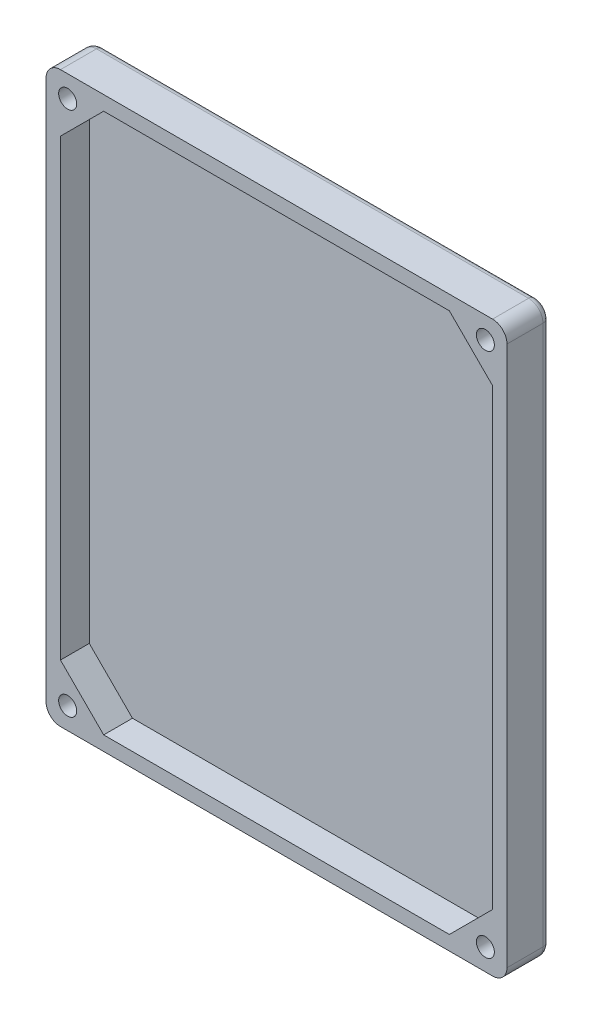
SolidWorks part; units mm, degrees
ref_plane "Front Plane" through (0, 0, 0) normal (0, 0, 1) x (1, 0, 0)
ref_plane "Top Plane" through (0, 0, 0) normal (0, 1, 0) x (1, 0, 0)
ref_plane "Right Plane" through (0, 0, 0) normal (1, 0, 0) x (0, 0, -1)
sketch "Sketch1" plane through (0, 0, 0) normal (0, 0, 1) x (1, 0, 0)
  line L1 (32, -39.5) -> (-32, -39.5)
  line L2 (32, -39.5) -> (32, 39.5)
  line L3 (32, 39.5) -> (-32, 39.5)
  line L4 (-32, -39.5) -> (-32, 39.5)
  line L5 (32, -39.5) -> (-32, 39.5) construction
  line L6 (32, 39.5) -> (-32, -39.5) construction
  point P0 (0, 0)
  dimension "D1" = 64
  dimension "D2" = 79
extrude "Boss-Extrude1" add sketch "Sketch1" along normal blind 2
sketch "Sketch2" plane through (0, 0, 2) normal (0, 0, 1) x (1, 0, 0)
  line L0 (-30, 31.5) -> (-24, 37.5)
  line L5 (24, -37.5) -> (-24, -37.5)
  line L6 (30, -31.5) -> (30, 31.5)
  line L7 (24, 37.5) -> (-24, 37.5)
  line L8 (-30, -31.5) -> (-30, 31.5)
  line L9 (30, -37.5) -> (-30, 37.5) construction
  line L10 (30, 37.5) -> (-30, -37.5) construction
  line L11 (-30, -31.5) -> (-24, -37.5)
  line L12 (24, -37.5) -> (30, -31.5)
  line L13 (30, 31.5) -> (24, 37.5)
  line L15 (32, -39.5) -> (-32, -39.5)
  line L16 (32, -39.5) -> (32, 39.5)
  line L17 (32, 39.5) -> (-32, 39.5)
  line L18 (-32, -39.5) -> (-32, 39.5)
  line L19 (32, -39.5) -> (-32, 39.5) construction
  line L20 (32, 39.5) -> (-32, -39.5) construction
  point P0 (0, 0)
  point P6 (0, 0)
  dimension "D2" = 2
  dimension "D3" = 6
  dimension "D4" = 6
  dimension "D5" = 6
  dimension "D6" = 6
  dimension "D7" = 6
  dimension "D8" = 6
  dimension "D9" = 6
  dimension "D10" = 6
  dimension "D11" = 2
  dimension "D12" = 2
  dimension "D13" = 2
extrude "Boss-Extrude6" add sketch "Sketch2" along normal blind 4
fillet "Fillet1" radius 2 1 edges at (-32, -39.5, 3)
fillet "Fillet2" radius 2 1 edges at (32, -39.5, 3)
fillet "Fillet3" radius 2 1 edges at (32, 39.5, 3)
fillet "Fillet4" radius 2 1 edges at (-32, 39.5, 3)
sketch "Sketch4" plane through (0, 0, 0) normal (0, 0, -1) x (-1, 0, 0)
  line L0 (32, 37.5) -> (32, -37.5) construction
  line L1 (-30, 39.5) -> (30, 39.5) construction
  line L2 (30, -39.5) -> (-30, -39.5) construction
  line L3 (-32, -37.5) -> (-32, 37.5) construction
  circle A0 centre (29, 36.5) radius 2
  circle A1 centre (29, -36.5) radius 2
  circle A2 centre (-29, -36.5) radius 2
  circle A3 centre (-29, 36.5) radius 2
  dimension "D1" = 4
  dimension "D2" = 4
  dimension "D3" = 4
  dimension "D4" = 4
  dimension "D5" = 3
  dimension "D6" = 3
  dimension "D7" = 3
  dimension "D8" = 3
  dimension "D9" = 3
  dimension "D10" = 3
  dimension "D11" = 3
  dimension "D12" = 3
extrude "Cut-Extrude1" cut sketch "Sketch4" against normal blind 2
sketch "Sketch6" plane through (0, 0, 2) normal (0, 0, -1) x (-1, 0, 0)
  circle A0 centre (29, 36.5) radius 1.25
  circle A1 centre (29, -36.5) radius 1.25
  circle A2 centre (-29, -36.5) radius 1.25
  circle A3 centre (-29, 36.5) radius 1.25
  dimension "D1" = 2.5
  dimension "D2" = 2.5
  dimension "D3" = 2.5
  dimension "D4" = 2.5
extrude "Cut-Extrude2" cut sketch "Sketch6" against normal blind 4
fillet "Fillet5" radius 1 8 edges at (0, -39.5, 0) (-31.4142, -38.9142, 0) (32, 0, 0) (31.4142, -38.9142, 0) (0, 39.5, 0) (31.4142, 38.9142, 0) (-32, 0, 0) (-31.4142, 38.9142, 0)
